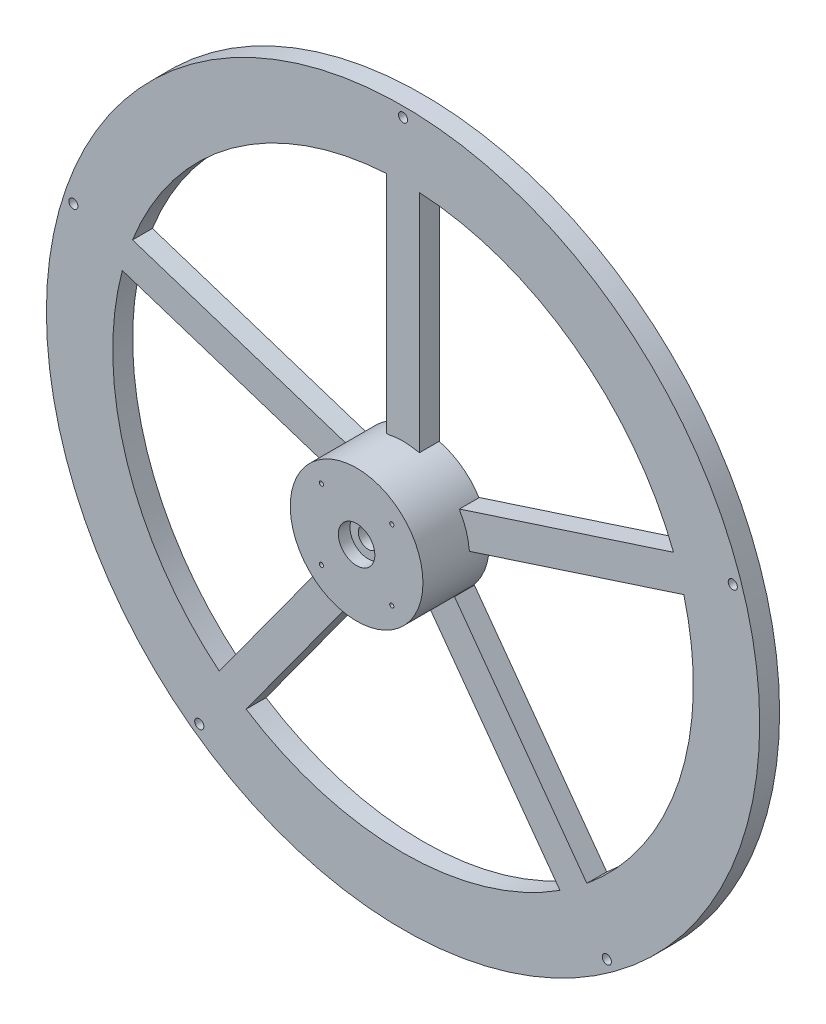
SolidWorks part; units mm, degrees
ref_plane "Front Plane" through (0, 0, 0) normal (0, 0, 1) x (1, 0, 0)
ref_plane "Top Plane" through (0, 0, 0) normal (0, 1, 0) x (1, 0, 0)
ref_plane "Right Plane" through (0, 0, 0) normal (1, 0, 0) x (0, 0, -1)
sketch "Sketch1" plane through (0, 0, 0) normal (0, 0, 1) x (1, 0, 0)
  circle A0 centre (0, 0) radius 215
  circle A1 centre (0, 0) radius 175
extrude "Ring" add sketch "Sketch1" along normal blind 12
sketch "Sketch2" plane through (0, 0, 0) normal (0, 0, 1) x (1, 0, 0)
  circle A0 centre (0, 0) radius 40
extrude "Hub" add sketch "Sketch2" along normal blind 40
sketch "Sketch3" plane through (0, 0, 0) normal (0, 0, 1) x (1, 0, 0)
  line L0 (40.1814, 2.5411) -> (170.4761, 44.8764)
  line L1 (170.4761, 44.8764) -> (164.2958, 63.8976)
  line L2 (164.2958, 63.8976) -> (34.001, 21.5622)
  line L3 (34.001, 21.5622) -> (40.1814, 2.5411)
  line L4 (10, 39) -> (10, 176)
  line L5 (10, 176) -> (-10, 176)
  line L6 (-10, 176) -> (-10, 39)
  line L7 (-10, 39) -> (10, 39)
  line L8 (-34.001, 21.5622) -> (-164.2958, 63.8976)
  line L9 (-164.2958, 63.8976) -> (-170.4761, 44.8764)
  line L10 (-170.4761, 44.8764) -> (-40.1814, 2.5411)
  line L11 (-40.1814, 2.5411) -> (-34.001, 21.5622)
  line L12 (-31.0138, -25.6738) -> (-111.5404, -136.5091)
  line L13 (-111.5404, -136.5091) -> (-95.36, -148.2648)
  line L14 (-95.36, -148.2648) -> (-14.8335, -37.4295)
  line L15 (-14.8335, -37.4295) -> (-31.0138, -25.6738)
  line L16 (14.8335, -37.4295) -> (95.36, -148.2648)
  line L17 (95.36, -148.2648) -> (111.5404, -136.5091)
  line L18 (111.5404, -136.5091) -> (31.0138, -25.6738)
  line L19 (31.0138, -25.6738) -> (14.8335, -37.4295)
extrude "Spokes" add sketch "Sketch3" along normal blind 12
sketch "Sketch4" plane through (0, 0, 0) normal (0, 0, 1) x (1, 0, 0)
  circle A0 centre (0, 0) radius 6
extrude "Bore" cut sketch "Sketch4" along normal blind 40
sketch "Sketch5" plane through (0, 0, 0) normal (0, 0, 1) x (1, 0, 0)
  circle A0 centre (0, 0) radius 11
extrude "Bearing_seat_low" cut sketch "Sketch5" along normal blind 7
ref_plane "Plane_z33" through (0, 0, 33) normal (0, 0, 1) x (1, 0, 0)
sketch "Sketch6" plane through (0, 0, 33) normal (0, 0, 1) x (1, 0, 0)
  circle A0 centre (0, 0) radius 11
extrude "Bearing_seat_high" cut sketch "Sketch6" along normal blind 7
sketch "Sketch7" plane through (0, 0, 0) normal (0, 0, 1) x (1, 0, 0)
  circle A0 centre (0, 0) radius 184
  circle A1 centre (0, 0) radius 179
extrude "Band_seat" cut sketch "Sketch7" along normal blind 3
sketch "Sketch8" plane through (0, 0, 0) normal (0, 0, 1) x (1, 0, 0)
  circle A0 centre (198.7708, 64.5846) radius 2.75
  circle A1 centre (0, 209) radius 2.75
  circle A2 centre (-198.7708, 64.5846) radius 2.75
  circle A3 centre (-122.8471, -169.0846) radius 2.75
  circle A4 centre (122.8471, -169.0846) radius 2.75
extrude "Rod_holes" cut sketch "Sketch8" along normal blind 12
ref_plane "Plane_z32" through (0, 0, 32) normal (0, 0, 1) x (1, 0, 0)
sketch "Sketch9" plane through (0, 0, 32) normal (0, 0, 1) x (1, 0, 0)
  circle A0 centre (21.2132, 21.2132) radius 1.25
  circle A1 centre (-21.2132, 21.2132) radius 1.25
  circle A2 centre (-21.2132, -21.2132) radius 1.25
  circle A3 centre (21.2132, -21.2132) radius 1.25
extrude "Grommet_screws" cut sketch "Sketch9" along normal blind 8
